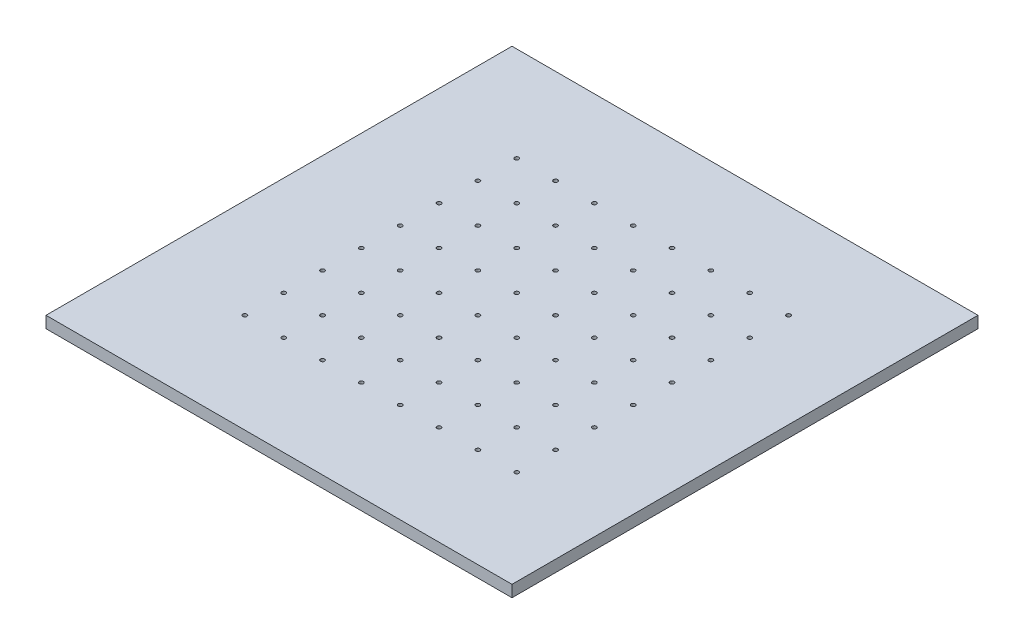
SolidWorks part; units mm, degrees
ref_plane "Front Plane" through (0, 0, 0) normal (0, 0, 1) x (1, 0, 0)
ref_plane "Top Plane" through (0, 0, 0) normal (0, 1, 0) x (1, 0, 0)
ref_plane "Right Plane" through (0, 0, 0) normal (1, 0, 0) x (0, 0, -1)
sketch "Sketch3" plane through (0, 0, 0) normal (0, 1, 0) x (1, 0, 0)
  line L1 (-300, -300) -> (300, -300)
  line L2 (-300, -300) -> (-300, 300)
  line L3 (-300, 300) -> (300, 300)
  line L4 (300, -300) -> (300, 300)
  line L5 (-300, -300) -> (300, 300) construction
  line L6 (-300, 300) -> (300, -300) construction
  point P0 (0, 0)
  dimension "D1" = 600
  dimension "D2" = 600
extrude "Boss-Extrude1" add sketch "Sketch3" along normal blind 15
sketch "Sketch4" plane through (0, 15, 0) normal (0, 1, 0) x (1, 0, 0)
  line L1 (203.4, 203.4) -> (-203.4, 203.4)
  line L2 (203.4, 203.4) -> (203.4, -203.4)
  line L3 (203.4, -203.4) -> (-203.4, -203.4)
  line L4 (-203.4, 203.4) -> (-203.4, -203.4)
  line L5 (203.4, 203.4) -> (-203.4, -203.4) construction
  line L6 (203.4, -203.4) -> (-203.4, 203.4) construction
  point P0 (0, 0)
  dimension "D1" = 406.8
  dimension "D2" = 406.8
sketch "Sketch5" plane through (0, 15, 0) normal (0, 1, 0) x (1, 0, 0)
  line L0 (203.4, 203.4) -> (-203.4, -203.4) construction
  line L1 (203.4, 203.4) -> (152.6, 203.4)
  line L2 (203.4, 203.4) -> (203.4, 152.6)
  line L3 (203.4, 152.6) -> (152.6, 152.6)
  line L4 (152.6, 203.4) -> (152.6, 152.6)
  circle A0 centre (178.0378, 178) radius 2.65
  dimension "D2" = 5.3
  dimension "D1" = 50.8
extrude "Cut-Extrude1" cut sketch "Sketch5" against normal blind 8.5 draft 1 contours A0
pattern_linear "LPattern1" count 8 spacing 50 along (-1, 0, 0) count 8 spacing 50 along (0, 0, 1) of "Cut-Extrude1"
